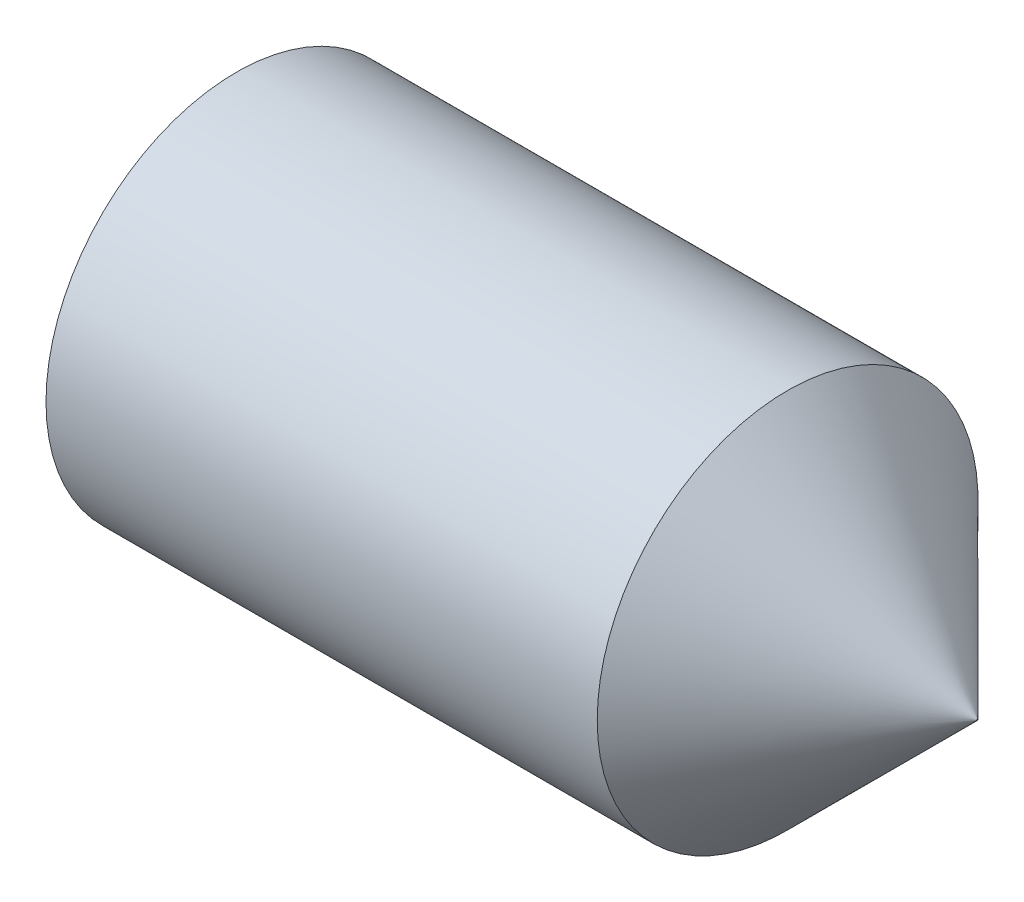
SolidWorks part; units mm, degrees
revolve "BaseBody" add sketch "BodySke" angle 360 about L5 other way angle 60
sketch "BodySke" plane through (0, 0, 0) normal (0, 0, 1) x (1, 0, 0)
  line L0 (0, 0) -> (0, 1.2195)
  line L1 (0, 1.2195) -> (0.1619, 1.5)
  line L2 (0.1619, 1.5) -> (4.505, 1.5)
  line L3 (6, 0) -> (6, 0.005)
  line L4 (6, 0) -> (0, 0)
  line L5 (-12.7, 0) -> (88.9, 0) construction
  line L6 (6, 0.005) -> (4.505, 1.5)
  line L7 (0.5, 15.875) -> (0.5, -3.175) construction
  line L8 (0, -1.2195) -> (0.1619, -1.5) construction
  line L9 (6, -0.005) -> (4.505, -1.5) construction
  dimension "Length" = 6
  dimension "Tip_dia" = 0.01
  dimension "Cone_ang" = 90
  dimension "Diameter" = 3
cosmetic thread "ThreadCosmetic" [suppressed] parameters "Thread_minor"=2.439
ref_plane "Plane1" through (0, 0, 0) normal (0, 0, 1) x (1, 0, 0)
ref_plane "Plane2" through (0, 0, 0) normal (0, 1, 0) x (1, 0, 0)
ref_plane "Plane3" through (0, 0, 0) normal (1, 0, 0) x (0, 0, -1)
sketch "Sketch2" plane through (0, 0, 0) normal (-1, 0, 0) x (0, 0, 1)
  line L0 (0.433, 0.75) -> (-0.433, 0.75)
  line L1 (-0.433, 0.75) -> (-0.866, 0)
  line L2 (0.433, 0.75) -> (0.866, 0)
  line L3 (0.433, -0.75) -> (0.866, 0)
  line L4 (0.433, -0.75) -> (-0.433, -0.75)
  line L5 (-0.433, -0.75) -> (-0.866, 0)
  dimension "D2" = 0.75
  dimension "D3" = 0.75
extrude "Hex" cut sketch "Sketch2" against normal blind 2.1
sketch "Sketch4" plane through (0, 4.7709, -0.5249) normal (-1, 0, 0) x (0, 0, 1)
  line L0 (0.5249, -4.7709) -> (1.3124, -4.7709)
  line L1 (0.5249, -4.7709) -> (6.6732, -1.2211) construction
  line L2 (0.5249, -4.7709) -> (0.9186, -4.0889)
  line L3 (1.153, -4.6137) -> (1.2782, -4.5415)
  line L4 (0.975, -4.3054) -> (1.1002, -4.2332)
  arc A0 (1.153, -4.6137) -> (0.975, -4.3054) centre (0.5249, -4.7709) ccw
  arc A1 (1.3124, -4.7709) -> (1.2782, -4.5415) centre (0.5249, -4.7709) ccw
  arc A2 (0.9186, -4.0889) -> (1.1002, -4.2332) centre (0.5249, -4.7709) cw
  circle A3 centre (0.5249, -4.7709) radius 0.6475 construction
  circle A4 centre (0.5249, -4.7709) radius 0.7875 construction
  dimension "Spline_n_dim" = 1.295
  dimension "Spline_m_dim" = 1.575
  dimension "D1" = 30
  dimension "Spline_p_dim" = 0.356
  dimension "D3" = 0.178
extrude "Spline6" [suppressed] cut sketch "Sketch4" against normal blind 1.2
pattern_circular "CirPattern1" [suppressed] count 6 every 60 about axis through (-12.7, 0, 0) along (1, 0, 0)
sketch "Sketch5" plane through (0, 1.4735, 6.925) normal (-1, 0, 0) x (0, 0, 1)
  line L0 (-6.925, -1.4735) -> (-6.1375, -1.4735)
  line L1 (-6.925, -1.4735) -> (-1.9049, 3.5466) construction
  line L2 (-6.925, -1.4735) -> (-6.925, -0.686)
  line L3 (-6.3413, -1.1415) -> (-6.2567, -1.0569)
  line L4 (-6.5931, -0.8898) -> (-6.5085, -0.8052)
  line L5 (-6.5931, -0.8898) -> (-6.3413, -1.1415)
  arc A1 (-6.1375, -1.4735) -> (-6.2567, -1.0569) centre (-6.925, -1.4735) ccw
  arc A2 (-6.925, -0.686) -> (-6.5085, -0.8052) centre (-6.925, -1.4735) cw
  circle A3 centre (-6.925, -1.4735) radius 0.6475 construction
  circle A4 centre (-6.925, -1.4735) radius 0.7875 construction
  dimension "Spline_n_dim" = 1.295
  dimension "Spline_m_dim" = 1.575
  dimension "Spline_p_dim" = 0.356
  dimension "D3" = 0.178
  dimension "D1" = 45
  dimension "Spline_a_dim" = 90
extrude "Spline4" [suppressed] cut sketch "Sketch5" against normal blind 1.2
pattern_circular "CirPattern2" [suppressed] count 4 every 90 about axis through (-12.7, 0, 0) along (1, 0, 0)
sketch "ThdSchSke" plane through (0, 0, 0) normal (0, 0, 1) x (1, 0, 0)
  line L0 (0.1619, -1.2195) -> (-0.0345, -1.5)
  line L1 (0.1619, -1.2195) -> (0.3584, -1.5)
  line L2 (0.3584, -1.5) -> (0.3584, -1.875)
  line L3 (-3.175, 0) -> (5.1513, 0) construction
  line L4 (0.1619, 1.5) -> (0.1619, -1.5) construction
  line L5 (0.3584, -1.875) -> (-0.0345, -1.875)
  line L6 (-0.0345, -1.875) -> (-0.0345, -1.5)
  dimension "Thread_minor" = 2.439
  dimension "Diameter" = 3
revolve "ThreadSchematic" [suppressed] cut sketch "ThdSchSke" angle 360 about L3
pattern_linear "ThdSchPat" [suppressed]
equation "\"D2@Sketch2\" = \"Hex_size@Sketch2\" / 2"
equation "\"D3@Sketch2\" = \"Hex_size@Sketch2\" / 2"
equation "\"Thread_minor@ThreadCosmetic\" = \"Minor_dia@BodySke\""
equation "\"D1@Sketch4\" = \"Spline_a_dim@Sketch4\" / 2"
equation "\"D3@Sketch4\" = \"Spline_p_dim@Sketch4\" / 2"
equation "\"D2@CirPattern1\" = \"Spline_a_dim@Sketch4\""
equation "\"Num_teeth@CirPattern1\" = 360 / \"D2@CirPattern1\""
equation "\"Spline_a_dim@Sketch5\" = 90"
equation "\"Spline_p_dim@Sketch5\" = \"Spline_p_dim@Sketch4\""
equation "\"Spline_m_dim@Sketch5\" = \"Spline_m_dim@Sketch4\""
equation "\"Spline_n_dim@Sketch5\" = \"Spline_n_dim@Sketch4\""
equation "\"D1@Sketch5\" = \"Spline_a_dim@Sketch5\" / 2"
equation "\"D3@Sketch5\" = \"Spline_p_dim@Sketch5\" / 2"
equation "\"Key_eng@Spline4\" = \"Key_eng@Spline6\""
equation "\"Thread_minor@ThdSchSke\" = \"Thread_minor@ThreadCosmetic\""
equation "\"Diameter@ThdSchSke\" = \"Diameter@BodySke\""
equation "\"Overcut@ThdSchSke\" = \"Diameter@BodySke\" * 1.25"
equation "\"Num_threads@ThdSchPat\" = int( (\"Length@BodySke\" - ( ( ( \"Diameter@BodySke\" - \"Minor_dia@BodySke\" ) * 0.5 ) / tan( \"Drive_ch_ang@BodySke\" * 0.017453292 ) ) - ( ( \"Diameter@BodySke\" * 0.5 ) / tan( \"Cone_ang@BodySke\" * 0.008726646 ) ) ) / \"Advance@BodySke\" + 0.999 )  + 1"
equation "\"Num_threads@ThdSchPat\" = int( (\"Length@BodySke\" - ( ( ( \"Diameter@BodySke\" - \"Minor_dia@BodySke\" ) * 0.5 ) / tan( \"Drive_ch_ang@BodySke\" * 0.017453292 ) ) - ( (( \"Diameter@BodySke\" - \"Tip_dia@BodySke\") * 0.5 ) / tan( \"Cone_ang@BodySke\" * 0.008726646 ) ) ) / \"Advance@BodySke\" + 0.999 )  + 1"
equation "\"Advance@ThdSchPat\" = (\"Length@BodySke\" - ( ( ( \"Diameter@BodySke\" - \"Minor_dia@BodySke\" ) * 0.5 ) / tan( \"Drive_ch_ang@BodySke\" * 0.017453292 ) ) - ( ( \"Diameter@BodySke\" * 0.5 ) / tan( \"Cone_ang@BodySke\" * 0.008726646 ) ) ) /  (\"Num_threads@ThdSchPat\" - 1) 'relax it"
equation "\"Advance@ThdSchPat\" = (\"Length@BodySke\" - ( ( ( \"Diameter@BodySke\" - \"Minor_dia@BodySke\" ) * 0.5 ) / tan( \"Drive_ch_ang@BodySke\" * 0.017453292 ) ) - ( ( (\"Diameter@BodySke\" - \"Tip_dia@BodySke\") * 0.5 ) / tan( \"Cone_ang@BodySke\" * 0.008726646 ) ) ) /  (\"Num_threads@ThdSchPat\" - 1) 'relax it"
equation "' \"Num_threads@ThdSchPat\" = \"Num_threads@ThdSchPat\" - sgn( \"Num_threads@ThdSchPat\" - 1) '---chamfered tips only---"
